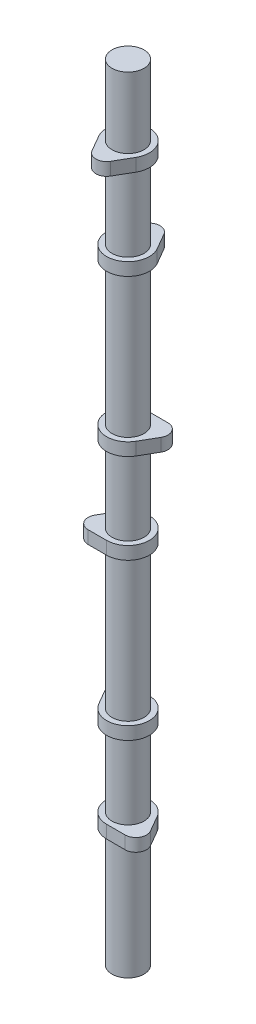
SolidWorks part; units mm, degrees
ref_plane "Front Plane" through (0, 0, 0) normal (0, 0, 1) x (1, 0, 0)
ref_plane "Top Plane" through (0, 0, 0) normal (0, 1, 0) x (1, 0, 0)
ref_plane "Right Plane" through (0, 0, 0) normal (1, 0, 0) x (0, 0, -1)
sketch "Sketch1" plane through (0, 0, 0) normal (0, 1, 0) x (1, 0, 0)
  line L0 (-10.9985, 6.35) -> (-5.4993, 15.875)
  line L1 (10.9985, 6.35) -> (5.4993, 15.875)
  arc A0 (-10.9985, 6.35) -> (10.9985, 6.35) centre (0, 0) ccw
  arc A1 (5.4993, 15.875) -> (-5.4993, 15.875) centre (0, 12.7) ccw
  dimension "D2" = 12.7
  dimension "D3" = 25.4
  dimension "D1" = 12.7
extrude "Boss-Extrude1" add sketch "Sketch1" along normal blind 7.62
ref_axis "Axis2" through (0, 22.5293, 0) along (0, -1, 0)
pattern_linear "LPattern1" count 2 spacing 53.34 along (0, 1, 0) of bodies 101
move or copy body "Body-Move/Copy1" bodies to move or copy 102 copy no rotation origin (0, 0, 0) rotation axis (0, 1, 0) rotation angle 180
pattern_linear "LPattern2" count 3 spacing 146.05 along (0, -1, 0) of bodies 103 101
move or copy body "Body-Move/Copy3" bodies to move or copy 106 104 copy no rotation origin (0, 0, 0) rotation axis (0, 1, 0) rotation angle 120
move or copy body "Body-Move/Copy4" bodies to move or copy 107 105 copy no rotation origin (0, 0, 0) rotation axis (0, -1, 0) rotation angle 120
sketch "Sketch2" plane through (0, 0, 0) normal (0, 1, 0) x (1, 0, 0)
  circle A0 centre (0, 0) radius 9.5
  dimension "D1" = 19
extrude "Boss-Extrude2" add sketch "Sketch2" against normal blind 466.09 from offset 102.87
